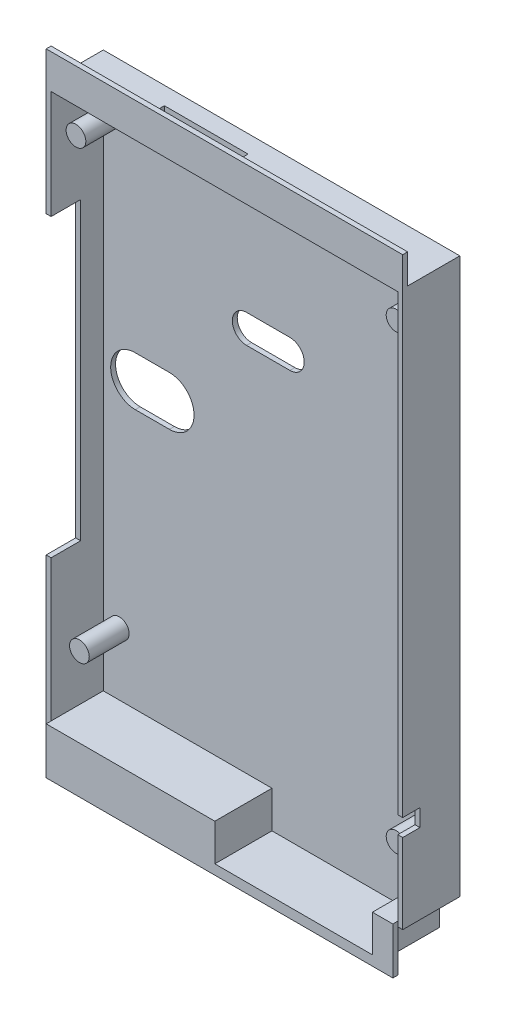
SolidWorks part; units mm, degrees
ref_plane "Plano frontal" through (0, 0, 0) normal (0, 0, 1) x (1, 0, 0)
ref_plane "Plano superior" through (0, 0, 0) normal (0, 1, 0) x (1, 0, 0)
ref_plane "Plano direito" through (0, 0, 0) normal (1, 0, 0) x (0, 0, -1)
sketch "Esboço1" plane through (0, 0, 0) normal (0, 0, 1) x (1, 0, 0)
  line L0 (11, 65.5) -> (171, 65.5) construction
  line L1 (0, 0) -> (182, 0)
  line L2 (0, 0) -> (0, 131)
  line L3 (0, 131) -> (182, 131)
  line L4 (182, 0) -> (182, 131)
  line L5 (11, 113.5) -> (171, 113.5)
  line L6 (11, 113.5) -> (11, 17.5)
  line L7 (11, 17.5) -> (171, 17.5)
  line L8 (171, 113.5) -> (171, 17.5)
  line L9 (5.7, 118.4) -> (176.3, 118.4)
  line L10 (5.7, 118.4) -> (5.7, 6.8)
  line L11 (5.7, 6.8) -> (176.3, 6.8)
  line L12 (176.3, 118.4) -> (176.3, 6.8)
  line L13 (5.9, 118.2) -> (176.1, 118.2)
  line L14 (5.9, 118.2) -> (5.9, 7)
  line L15 (5.9, 7) -> (176.1, 7)
  line L16 (176.1, 118.2) -> (176.1, 7)
  line L17 (91, 131) -> (91, 0) construction
  point P21 (91, 65.5)
  point P22 (91, 65.5)
  dimension "D1" = 131
  dimension "D2" = 182
  dimension "D3" = 160
  dimension "D4" = 96
  dimension "D5" = 170.2
  dimension "D6" = 111.2
  dimension "D7" = 0.2
  dimension "D8" = 4.7
  dimension "D9" = 0.2
  dimension "D10" = 0.2
  dimension "D11" = 0.2
  dimension "D12" = 5.1
  dimension "D13" = 5.1
  dimension "D14" = 10.5
extrude "Ressalto-extrusão1" add sketch "Esboço1" along normal blind 0.9 contours L16 L15 L14 L13
sketch "Esboço4" plane through (0, 0, 0) normal (0, 0, -1) x (-1, 0, 0)
  line L1 (-179.1, 121.2) -> (-2.9, 121.2)
  line L2 (-179.1, 121.2) -> (-179.1, 4)
  line L3 (-179.1, 4) -> (-2.9, 4)
  line L4 (-2.9, 121.2) -> (-2.9, 4)
  line L8 (-176.1, 118.2) -> (-176.1, 7) construction
  line L9 (-5.9, 118.2) -> (-176.1, 118.2) construction
  line L10 (-5.9, 7) -> (-176.1, 7) construction
  line L11 (-5.9, 118.2) -> (-5.9, 7) construction
  dimension "D1" = 3
  dimension "D2" = 3
  dimension "D3" = 3
  dimension "D4" = 3
extrude "Ressalto-extrusão3" add sketch "Esboço4" along normal blind 1
sketch "Esboço5" plane through (0, 4, 0) normal (0, -1, 0) x (1, 0, 0)
  line L0 (179.1, -1) -> (2.9, -1) construction
  line L1 (75, -1) -> (107, -1)
  line L2 (75, -1) -> (75, 0.9)
  line L3 (75, 0.9) -> (107, 0.9)
  line L4 (107, -1) -> (107, 0.9)
  line L5 (5.9, 0.9) -> (176.1, 0.9) construction
  point P8 (91, -1)
  point P9 (91, -1)
  dimension "D1" = 32
extrude "Corte-extrusão3" cut sketch "Esboço5" against normal blind 5
sketch "Esboço6" plane through (0, 0, -1) normal (0, 0, -1) x (-1, 0, 0)
  line L0 (-43.3, 106.45) -> (-42.05, 106.45) construction
  line L1 (-44, 16.15) -> (-44, 14.9) construction
  line L2 (-110.15, 109) -> (-40.75, 109) construction
  line L3 (-110.15, 109) -> (-110.15, 8.4) construction
  line L4 (-110.15, 8.4) -> (-40.75, 8.4) construction
  line L5 (-40.75, 109) -> (-40.75, 8.4) construction
  line L6 (-44, 16.15) -> (-42.75, 16.15) construction
  line L7 (-43.3, 106.45) -> (-43.3, 107.7) construction
  line L8 (-108.3, 106.45) -> (-108.3, 107.7) construction
  line L9 (-108.3, 106.45) -> (-109.55, 106.45) construction
  line L10 (-108.3, 14.75) -> (-108.3, 13.5) construction
  line L11 (-108.3, 14.75) -> (-109.55, 14.75) construction
  line L12 (-75, 9) -> (-107, 9) construction
  line L13 (-108.3, 14.75) -> (-108.3, 16) construction
  circle A0 centre (-108.3, 14.75) radius 1.25
  circle A1 centre (-108.3, 106.45) radius 1.25
  circle A2 centre (-43.3, 106.45) radius 1.25
  circle A3 centre (-44, 16.15) radius 1.25
  point P22 (-91, 9)
  dimension "D1" = 2.5
  dimension "D2" = 2.5
  dimension "D3" = 2.5
  dimension "D4" = 2.5
  dimension "D5" = 100.6
  dimension "D6" = 69.4
  dimension "D7" = 6.5
  dimension "D8" = 2
  dimension "D9" = 1.3
  dimension "D10" = 1.3
  dimension "D11" = 2.6
  dimension "D12" = 0.6
  dimension "D13" = 0.6
  dimension "D14" = 5.1
  dimension "D15" = 19.15
  dimension "D16" = 9
sketch "Esboço7" plane through (0, 0, -1) normal (0, 0, -1) x (-1, 0, 0)
  line L0 (-111.15, 121.2) -> (-40.75, 121.2)
  line L4 (-2.9, 121.2) -> (-179.1, 121.2) construction
  line L5 (-111.15, 121.2) -> (-111.15, 114.2)
  line L6 (-111.15, 114.2) -> (-40.75, 114.2)
  line L7 (-40.75, 114.2) -> (-40.75, 121.2)
  line L8 (-111.15, 114.2) -> (-111.15, 2.5)
  line L9 (-111.15, 2.5) -> (-111.15, -6)
  line L10 (-111.15, -6) -> (-40.75, -6)
  line L11 (-40.75, -6) -> (-40.75, 2.5)
  line L13 (-40.75, 114.2) -> (-40.75, 2.5)
  line L14 (-111.15, 115.2) -> (-40.75, 115.2)
  line L15 (-111.15, 2.5) -> (-108, 2.5)
  line L16 (-108, 2.5) -> (-108, -5)
  line L17 (-108, -5) -> (-74, -5)
  line L18 (-74, -5) -> (-74, 2.5)
  line L19 (-74, 2.5) -> (-40.75, 2.5)
  line L20 (-110.15, 109) -> (-110.15, 8.4) construction
  line L21 (-111.15, 3.5) -> (-107, 3.5)
  line L22 (-107, 3.5) -> (-107, -4)
  line L23 (-107, -4) -> (-75, -4)
  line L24 (-75, -4) -> (-75, 3.5)
  line L25 (-75, 3.5) -> (-40.75, 3.5)
  line L26 (-107, 9) -> (-107, 4) construction
  line L27 (-75, 9) -> (-75, 4) construction
  line L28 (-40.75, 109) -> (-40.75, 8.4) construction
  line L31 (-75, 4) -> (-2.9, 4) construction
  line M24 (-75, 9) -> (-75, 4)
  line M25 (-75, 4) -> (-2.9, 4)
  line M27 (-2.9, 121.2) -> (-179.1, 121.2)
  line M29 (-179.1, 4) -> (-107, 4)
  line M30 (-107, 4) -> (-107, 9)
  line M31 (-107, 9) -> (-75, 9)
  dimension "D1" = 7
  dimension "D2" = 10
  dimension "D3" = 1
  dimension "D4" = 1
  dimension "D5" = 1
  dimension "D6" = 1
  dimension "D7" = 1
  dimension "D8" = 1
  dimension "D9" = 1
  dimension "D10" = 2
  dimension "D11" = 0.5
extrude "Ressalto-extrusão4" add sketch "Esboço7" along normal blind 1 contours L5 L14 L7 M27 | L14 L5 L6 L7 region at (75.95, 118.2, -1) region at (75.95, 114.7, -1)
extrude "Ressalto-extrusão5" add sketch "Esboço7<3>" along normal blind 11.6 contours L14 L5 L6 L7 region at (75.95, 114.7, -1)
sketch "Esboço7<3>" plane through (0, 0, -1) normal (0, 0, -1) x (-1, 0, 0) same geometry as "Esboço7"
extrude "Ressalto-extrusão6" add sketch "Esboço7<4>" against normal blind 1 from surface contours L13 L6 L8 M29 M30 M31 M24 M25 | L24 L25 L13 L8 L21 L22 L23 M25 M24 M31 M30 M29 | L25 L24 L23 L22 L21 L8 L15 L16 L17 L18 L19 L13 region at (75.6331, 60.2076, -1) region at (89.7827, 2.5551, -1) region at (109.075, 2.7909, -1) starting at face at (75.95, 114.7, -12.6)
sketch "Esboço7<4>" plane through (0, 0, -1) normal (0, 0, -1) x (-1, 0, 0) same geometry as "Esboço7"
extrude "Ressalto-extrusão7" add sketch "Esboço7<5>" along normal up to surface (11.6 mm away) and the other way blind 1 contours L25 L24 L23 L22 L21 L8 L15 L16 L17 L18 L19 L13 region at (109.075, 2.7909, -1) up to face at (83.475, 28.8, -12.6)
sketch "Esboço7<5>" plane through (0, 0, -1) normal (0, 0, -1) x (-1, 0, 0) same geometry as "Esboço7"
extrude "Ressalto-extrusão8" add sketch "Esboço7<6>" along normal blind 1 from surface contours L19 L18 L17 L16 L15 L9 L10 L11 region at (64.7743, -2.1213, -1) starting at face at (85.9833, 0.5, 0)
sketch "Esboço7<6>" plane through (0, 0, -1) normal (0, 0, -1) x (-1, 0, 0) same geometry as "Esboço7"
sketch "Esboço8" plane through (111.15, 0, 0) normal (1, 0, 0) x (0, 0, -1)
  line L0 (1, 121.2) -> (2, 121.2)
  line L1 (2, 121.2) -> (2, 115.2)
  line L2 (2, 115.2) -> (12.6, 115.2)
  line L3 (12.6, 115.2) -> (12.6, 2.5)
  line L4 (12.6, 2.5) -> (1, 2.5)
  line L5 (1, 2.5) -> (1, 121.2)
extrude "Ressalto-extrusão9" add sketch "Esboço8" along normal blind 1
sketch "Esboço9" plane through (40.75, 0, 0) normal (-1, 0, 0) x (0, 0, 1)
  line L0 (-2, 121.2) -> (-1, 121.2)
  line L1 (-1, 121.2) -> (-1, 2.5)
  line L2 (-1, 2.5) -> (-12.6, 2.5)
  line L3 (-12.6, 2.5) -> (-12.6, 115.2)
  line L4 (-12.6, 115.2) -> (-2, 115.2)
  line L5 (-2, 115.2) -> (-2, 121.2)
extrude "Ressalto-extrusão10" add sketch "Esboço9" along normal blind 1
sketch "Esboço11" plane through (39.75, 0, 0) normal (-1, 0, 0) x (0, 0, 1)
  line L0 (-1, 4) -> (-1, 121.2) construction
  line L1 (-1, 92.2) -> (-7, 92.2)
  line L2 (-1, 92.2) -> (-1, 32.2)
  line L3 (-1, 32.2) -> (-7, 32.2)
  line L4 (-7, 92.2) -> (-7, 32.2)
  line L5 (-2, 115.2) -> (-12.6, 115.2) construction
  dimension "D1" = 23
  dimension "D2" = 60
  dimension "D3" = 6
extrude "Corte-extrusão4" cut sketch "Esboço11" against normal blind 1
sketch "Esboço12" plane through (112.15, 0, 0) normal (1, 0, 0) x (0, 0, -1)
  line L0 (1, 22.2068) -> (4.5, 22.2068)
  line L1 (1, 121.2) -> (1, 4) construction
  line L2 (4.5, 22.2068) -> (4.5, 18.7068)
  line L3 (4.5, 18.7068) -> (1, 18.7068)
  line L4 (1, 18.7068) -> (1, 22.2068)
  dimension "D1" = 3.5
  dimension "D2" = 3.5
extrude "Corte-extrusão5" cut sketch "Esboço12" against normal blind 1
sketch "Esboço13" plane through (0, 115.2, 0) normal (0, 1, 0) x (1, 0, 0)
  line L0 (39.75, 2) -> (112.15, 2) construction
  line L1 (72.75, 2) -> (55.75, 2)
  line L2 (72.75, 2) -> (72.75, 9)
  line L3 (72.75, 9) -> (55.75, 9)
  line L4 (55.75, 2) -> (55.75, 9)
  line L5 (39.75, 2) -> (39.75, 12.6) construction
  point P8 (72.75, 5.5)
  dimension "D1" = 16
  dimension "D2" = 17
  dimension "D3" = 7
extrude "Corte-extrusão6" cut sketch "Esboço13" against normal blind 1
sketch "Esboço14" plane through (0, 0, -12.6) normal (0, 0, -1) x (-1, 0, 0)
  line L0 (-54.1785, 61.2) -> (-47.2458, 61.2) construction
  line L1 (-54.1785, 66.2) -> (-47.2458, 66.2)
  line L2 (-54.1785, 56.2) -> (-47.2458, 56.2)
  line L4 (-39.75, 121.2) -> (-112.15, 121.2) construction
  arc A0 (-54.1785, 66.2) -> (-54.1785, 56.2) centre (-54.1785, 61.2) ccw
  arc A1 (-47.2458, 56.2) -> (-47.2458, 66.2) centre (-47.2458, 61.2) ccw
  point P2 (-50.7121, 61.2)
  dimension "D1" = 65
  dimension "D3" = 55
extrude "Corte-extrusão7" cut sketch "Esboço14" against normal blind 1
sketch "Esboço15" plane through (0, 0, -12.6) normal (0, 0, -1) x (-1, 0, 0)
  line L0 (-77.25, 81.7) -> (-71.25, 81.7) construction
  line L1 (-77.25, 83.2) -> (-71.25, 83.2) construction
  line L2 (-77.25, 80.2) -> (-71.25, 80.2) construction
  line L3 (-39.75, 121.2) -> (-112.15, 121.2) construction
  line L4 (-78.65, 81.7) -> (-69.85, 81.7) construction
  line L5 (-78.65, 84.6) -> (-69.85, 84.6)
  line L6 (-78.65, 78.8) -> (-69.85, 78.8)
  arc A0 (-77.25, 83.2) -> (-77.25, 80.2) centre (-77.25, 81.7) ccw construction
  arc A1 (-71.25, 80.2) -> (-71.25, 83.2) centre (-71.25, 81.7) ccw construction
  arc A2 (-78.65, 84.6) -> (-78.65, 78.8) centre (-78.65, 81.7) ccw
  arc A3 (-69.85, 78.8) -> (-69.85, 84.6) centre (-69.85, 81.7) ccw
  point P2 (-74.25, 81.7)
  point P11 (-74.25, 81.7)
  point P17 (-69.75, 81.7)
  point P18 (-78.75, 81.7)
  point P19 (-75.75, 81.7)
  dimension "D3" = 6
  dimension "D1" = 3
  dimension "D2" = 39.5
  dimension "D4" = 39
extrude "Corte-extrusão8" cut sketch "Esboço15" against normal blind 1
sketch "Esboço17" plane through (179.1, 0, 0) normal (1, 0, 0) x (0, 0, -1)
  line L1 (1, 4) -> (-39.8076, 4)
  line L2 (1, 4) -> (1, 157.8288)
  line L3 (1, 157.8288) -> (-39.8076, 157.8288)
  line L4 (-39.8076, 4) -> (-39.8076, 157.8288)
extrude "Corte-extrusão9" cut sketch "Esboço17" against normal through all both and the other way through all
sketch "Esboço18" plane through (0, 0, -11.6) normal (0, 0, 1) x (1, 0, 0)
  circle A0 centre (43.3, 106.45) radius 2
  circle A1 centre (108.3, 106.45) radius 2
  circle A2 centre (108.3, 14.75) radius 2
  circle A3 centre (44, 16.15) radius 2
  dimension "D1" = 4
  dimension "D2" = 4
  dimension "D3" = 4
  dimension "D4" = 4
extrude "Ressalto-extrusão11" add sketch "Esboço18" along normal blind 8.1
